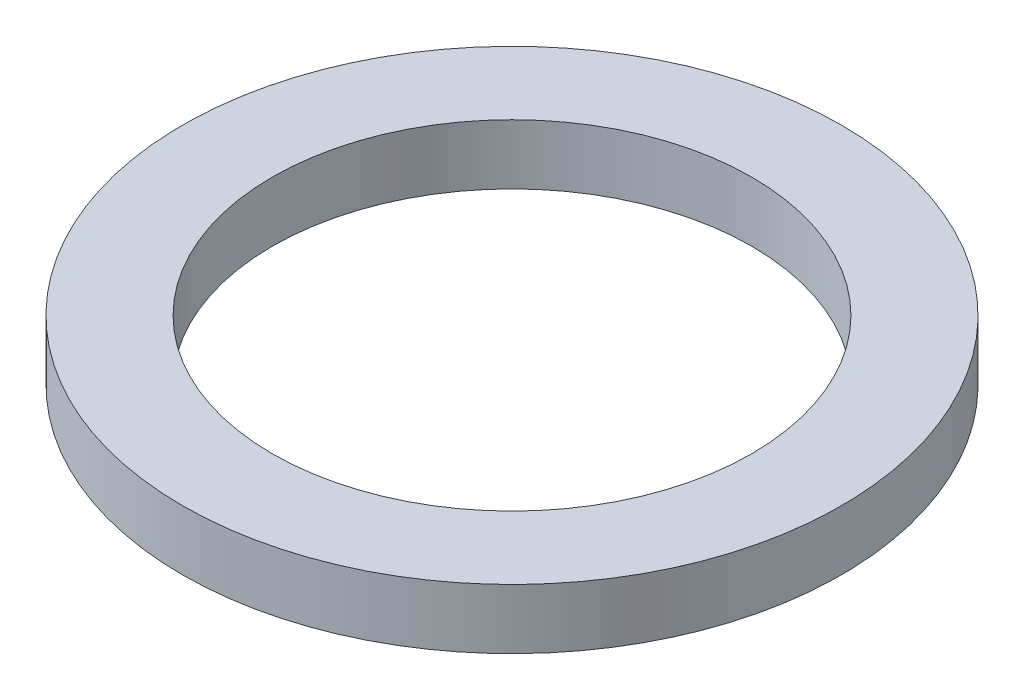
SolidWorks part; units mm, degrees
ref_plane "Front Plane" through (0, 0, 0) normal (0, 0, 1) x (1, 0, 0)
ref_plane "Top Plane" through (0, 0, 0) normal (0, 1, 0) x (1, 0, 0)
ref_plane "Right Plane" through (0, 0, 0) normal (1, 0, 0) x (0, 0, -1)
sketch "Sketch1" plane through (0, 0, 0) normal (0, 1, 0) x (1, 0, 0)
  circle A0 centre (0, 0) radius 27.5
  dimension "FLANGE_OD" = 55
extrude "Boss-Extrude1" add sketch "Sketch1" along normal blind 5
sketch "Sketch2" plane through (0, 0, 0) normal (0, 1, 0) x (1, 0, 0)
  circle A0 centre (0, 0) radius 20
  dimension "BORE_D" = 40
extrude "Cut-Extrude1" cut sketch "Sketch2" along normal through all
sketch "Sketch3" plane through (0, 5, 0) normal (0, 1, 0) x (1, 0, 0)
  circle A0 centre (0, 0) radius 11.5902 construction
  circle A1 centre (-11.5902, 0) radius 1.5
  dimension "BOLT_D" = 3
  dimension "BOLT_PCD" = 23.1804
extrude "Cut-Extrude2" cut sketch "Sketch3" against normal blind 3.2727 rebuild error yes
pattern_circular "CirPattern1" count 8 over 360 rebuild error yes
